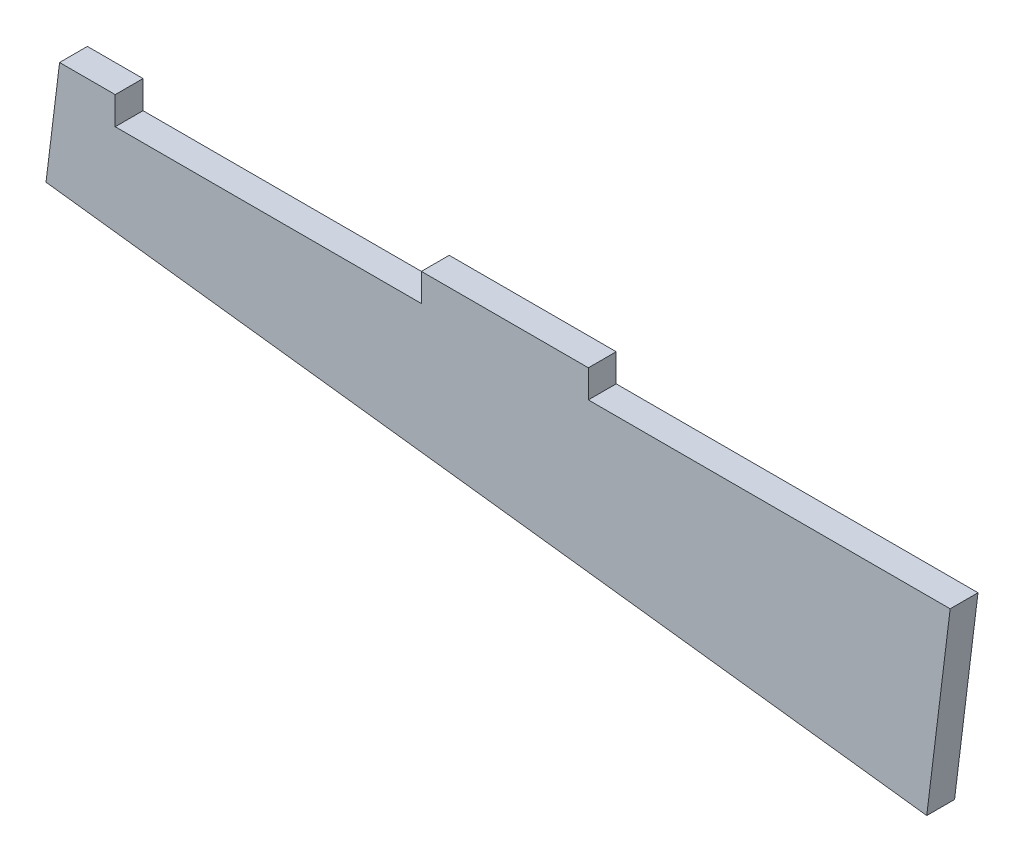
SolidWorks part; units mm, degrees
ref_plane "Front Plane" through (0, 0, 0) normal (0, 0, 1) x (1, 0, 0)
ref_plane "Top Plane" through (0, 0, 0) normal (0, 1, 0) x (1, 0, 0)
ref_plane "Right Plane" through (0, 0, 0) normal (1, 0, 0) x (0, 0, -1)
sketch "Sketch1" plane through (0, 0, 0) normal (0, 0, 1) x (1, 0, 0)
  line L0 (-195.3168, -62.6592) -> (-182.6168, -62.6592)
  line L4 (-182.6168, -62.6592) -> (-182.6168, -69.0092)
  line L5 (-182.6168, -69.0092) -> (-112.7668, -69.0092)
  line L6 (-112.7668, -69.0092) -> (-112.7668, -62.6592)
  line L7 (-112.7668, -62.6592) -> (-74.6668, -62.6592)
  line L8 (-74.6668, -62.6592) -> (-74.6668, -69.0092)
  line L9 (-74.6668, -69.0092) -> (7.8832, -69.0092)
  line L10 (7.8832, -69.0092) -> (2.5379, -112.5435)
  line L11 (2.5379, -112.5435) -> (-198.4122, -87.8699)
  line L12 (-198.4122, -87.8699) -> (-195.3168, -62.6592)
  line L13 (-357.854, -52.9756) -> (35.846, -101.3159) construction
  dimension "D1" = 12.7
  dimension "D2" = 6.35
  dimension "D3" = 69.85
  dimension "D4" = 38.1
  dimension "D5" = 82.55
  dimension "D6" = 25.4
extrude "Boss-Extrude1" add sketch "Sketch1" against normal blind 6.35
